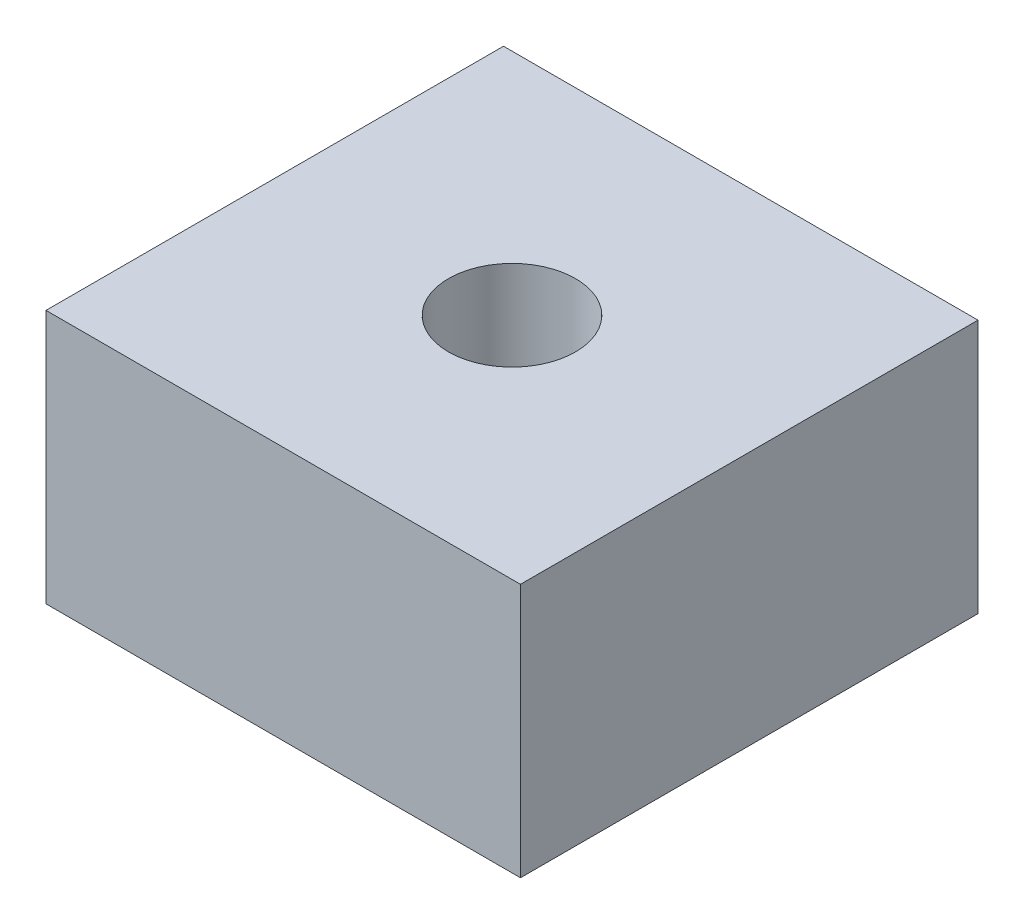
SolidWorks part; units mm, degrees
ref_plane "Front Plane" through (0, 0, 0) normal (0, 0, 1) x (1, 0, 0)
ref_plane "Top Plane" through (0, 0, 0) normal (0, 1, 0) x (1, 0, 0)
ref_plane "Right Plane" through (0, 0, 0) normal (1, 0, 0) x (0, 0, -1)
sketch "Sketch1" plane through (0, 0, 0) normal (0, 1, 0) x (1, 0, 0)
  line L1 (-2.8, -2.7) -> (2.8, -2.7)
  line L2 (-2.8, -2.7) -> (-2.8, 2.7)
  line L3 (-2.8, 2.7) -> (2.8, 2.7)
  line L4 (2.8, -2.7) -> (2.8, 2.7)
  line L5 (-2.8, -2.7) -> (2.8, 2.7) construction
  line L6 (-2.8, 2.7) -> (2.8, -2.7) construction
  circle A0 centre (0, 0) radius 0.75
  point P0 (0, 0)
  dimension "D1" = 1.5
  dimension "D2" = 5.6
  dimension "D3" = 5.4
extrude "Boss-Extrude1" add sketch "Sketch1" along normal blind 3
